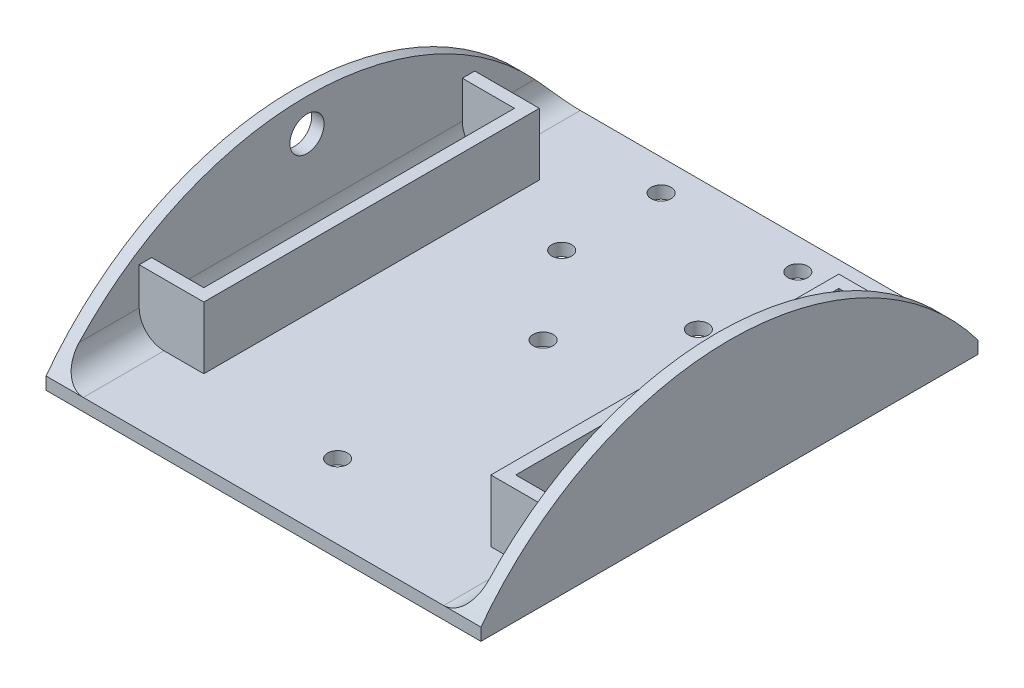
SolidWorks part; units mm, degrees
ref_plane "Front Plane" through (0, 0, 0) normal (0, 0, 1) x (1, 0, 0)
ref_plane "Top Plane" through (0, 0, 0) normal (0, 1, 0) x (1, 0, 0)
ref_plane "Right Plane" through (0, 0, 0) normal (1, 0, 0) x (0, 0, -1)
sketch "Sketch1" plane through (0, 0, 0) normal (0, 1, 0) x (1, 0, 0)
  line L1 (0, 0) -> (88.9, 0)
  line L2 (0, 0) -> (0, 101.6)
  line L3 (0, 101.6) -> (88.9, 101.6)
  line L4 (88.9, 0) -> (88.9, 101.6)
  dimension "D1" = 88.9
  dimension "D2" = 101.6
extrude "Base Extrude" add sketch "Sketch1" along normal blind 2.54
sketch "Sketch2" plane through (88.9, 0, 0) normal (1, 0, 0) x (0, 0, -1)
  line L2 (0, 2.54) -> (101.6, 2.54) construction
  line L3 (101.6, 2.54) -> (101.6, 0)
  line L4 (101.6, 0) -> (0, 0)
  line L5 (0, 0) -> (0, 2.54)
  arc A1 (0, 2.54) -> (101.6, 2.54) centre (50.8, -35.56) cw
  point P6 (50.8, 27.94)
  dimension "D1" = 25.4
extrude "Wall Extrude" add sketch "Sketch2" against normal blind 2.54 contours A1 L3 L4 L5
ref_plane "Wall Plane" through (44.45, 0, 0) normal (1, 0, 0) x (0, 0, -1)
mirror "Wall Mirror" about plane through (44.45, 0, 0) normal (1, 0, 0) of "Wall Extrude"
sketch "Sketch3" plane through (0, 0, 0) normal (-1, 0, 0) x (0, 0, 1)
  line L0 (-50.8, 27.94) -> (-50.8, -0.5285) construction
  circle A0 centre (-50.8, 21.2725) radius 3.4925
  arc A1 (0, 2.54) -> (-101.6, 2.54) centre (-50.8, -35.56) ccw construction
  dimension "D1" = 6.985
  dimension "D2" = 6.6675
extrude "Cut-Extrude1" cut sketch "Sketch3" against normal up to next
fillet "Fillet2" radius 5.08 2 edges at (2.54, 2.54, -50.8) (86.36, 2.54, -50.8)
sketch "Sketch4" plane through (0, 2.54, 0) normal (0, 1, 0) x (1, 0, 0)
  line L0 (44.45, 0) -> (44.45, 101.6) construction
  line L1 (0, 0) -> (88.9, 0) construction
  line L2 (88.9, 101.6) -> (0, 101.6) construction
  line L3 (44.45, 15.15) -> (44.45, 57.15) construction
  line L4 (88.9, 50.8) -> (0, 50.8) construction
  line L5 (88.9, 0) -> (88.9, 101.6) construction
  line L6 (0, 101.6) -> (0, 0) construction
  line L7 (81.28, 101.6) -> (7.62, 101.6) construction
  circle A0 centre (44.45, 57.15) radius 2.032
  circle A1 centre (44.45, 15.15) radius 2.032
  circle A3 centre (58.42, 74.93) radius 2.032
  circle A4 centre (58.42, 95.25) radius 2.032
  circle A5 centre (30.48, 74.93) radius 2.032
  circle A6 centre (30.48, 95.25) radius 2.032
  point P8 (0, 0)
  point P19 (0, 0)
  point P25 (0, 0)
  point P26 (51.429, 99.4979)
  dimension "D1" = 4.064
  dimension "D2" = 42
  dimension "D4" = 13.97
  dimension "D3" = 44.45
  dimension "D5" = 20.32
  dimension "D6" = 6.35
extrude "Cut-Extrude2" cut sketch "Sketch4" against normal through all
sketch "Sketch5" plane through (0, 2.54, 0) normal (0, 1, 0) x (1, 0, 0)
  line L0 (2.54, 4.241) -> (2.54, 97.359) construction
  line L1 (13.208, 19.05) -> (2.54, 19.05)
  line L2 (13.208, 19.05) -> (13.208, 82.55)
  line L3 (13.208, 82.55) -> (2.54, 82.55)
  line L4 (2.54, 19.05) -> (2.54, 82.55)
  line L5 (44.45, 101.6) -> (44.45, 0) construction
  line L6 (15.748, 85.09) -> (2.54, 85.09)
  line L7 (15.748, 85.09) -> (15.748, 16.51)
  line L8 (15.748, 16.51) -> (2.54, 16.51)
  line L9 (2.54, 85.09) -> (2.54, 16.51)
  line L10 (81.28, 101.6) -> (7.62, 101.6) construction
  line L11 (7.62, 0) -> (81.28, 0) construction
  line L12 (88.9, 0) -> (88.9, 101.6) construction
  line L13 (88.9, 86.36) -> (75.692, 86.36)
  line L14 (88.9, 86.36) -> (88.9, 15.24)
  line L19 (88.9, 15.24) -> (75.692, 15.24)
  line L24 (75.692, 86.36) -> (75.692, 15.24)
  line L25 (88.9, 50.8) -> (0, 50.8) construction
  line L26 (0, 101.6) -> (0, 0) construction
  line L27 (86.36, 97.359) -> (86.36, 4.241) construction
  line L28 (88.9, 52.07) -> (75.692, 52.07)
  line L29 (88.9, 52.07) -> (88.9, 49.53)
  line L30 (88.9, 49.53) -> (75.692, 49.53)
  line L31 (75.692, 52.07) -> (75.692, 49.53)
  line L32 (78.232, 17.78) -> (86.36, 17.78)
  line L33 (78.232, 17.78) -> (78.232, 83.82)
  line L34 (78.232, 83.82) -> (86.36, 83.82)
  line L35 (86.36, 17.78) -> (86.36, 83.82)
  line L36 (86.36, 86.36) -> (86.36, 15.24)
  point P6 (13.208, 50.8)
  point P9 (2.54, 50.8)
  point P28 (44.45, 50.8)
  point P29 (44.45, 50.8)
  dimension "D1" = 63.5
  dimension "D2" = 2.54
  dimension "D3" = 2.54
  dimension "D4" = 68.58
  dimension "D5" = 10.668
  dimension "D6" = 13.208
  dimension "D7" = 71.12
  dimension "D8" = 2.54
  dimension "D9" = 1.27
  dimension "D10" = 2.54
  dimension "D11" = 2.54
  dimension "D12" = 2.54
extrude "Boss-Extrude1" add sketch "Sketch5" along normal blind 12.7
